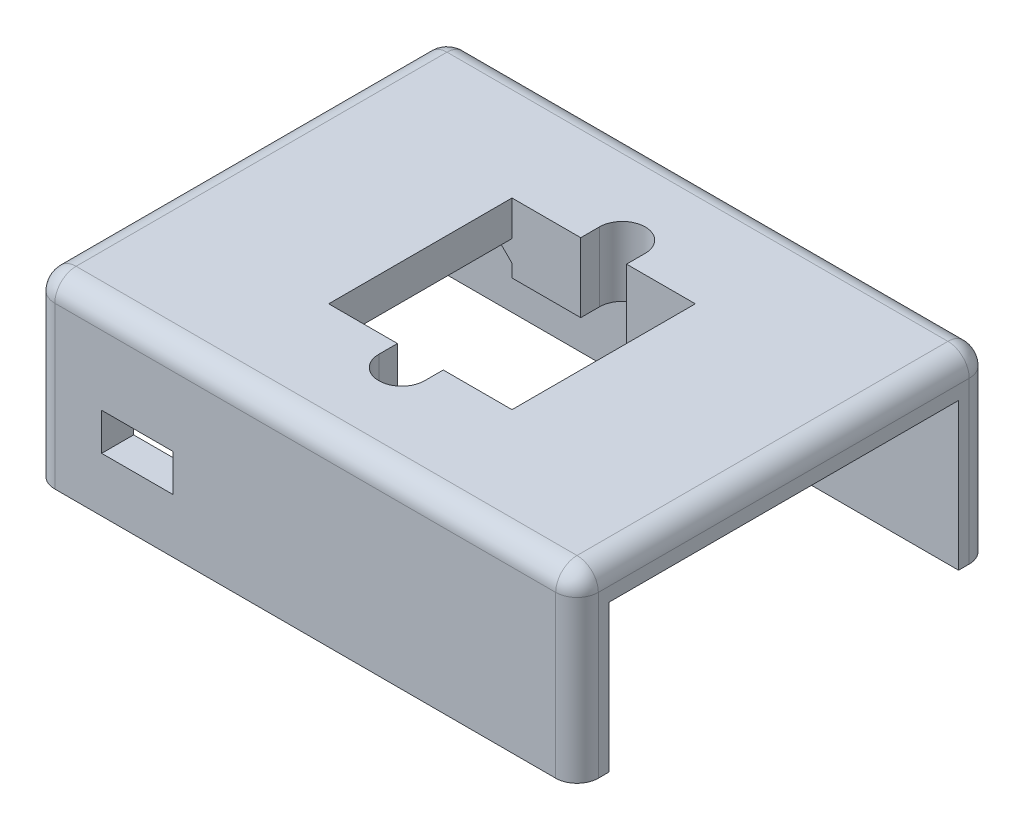
SolidWorks part; units mm, degrees
ref_plane "Alzado" through (0, 0, 0) normal (0, 0, 1) x (1, 0, 0)
ref_plane "Planta" through (0, 0, 0) normal (0, 1, 0) x (1, 0, 0)
ref_plane "Vista lateral" through (0, 0, 0) normal (1, 0, 0) x (0, 0, -1)
sketch "Croquis2" plane through (0, 0, 0) normal (0, 1, 0) x (1, 0, 0)
  line L1 (-30.5451, 30.6697) -> (20.4549, 30.6697)
  line L2 (-30.5451, 30.6697) -> (-30.5451, -8.1303)
  line L3 (-30.5451, -8.1303) -> (20.4549, -8.1303)
  line L4 (20.4549, 30.6697) -> (20.4549, -8.1303)
  dimension "D1" = 38.8
  dimension "D2" = 51
extrude "Saliente-Extruir2" add sketch "Croquis2" along normal blind 12.5
sketch "Croquis8" plane through (0, 0, 0) normal (0, -1, 0) x (1, 0, 0)
  line L0 (-30.5451, -30.6697) -> (-30.5451, 8.1303) construction
  line L1 (-27.5451, 5.1303) -> (17.4549, 5.1303)
  line L2 (-27.5451, 5.1303) -> (-27.5451, -27.6697)
  line L3 (-27.5451, -27.6697) -> (17.4549, -27.6697)
  line L4 (17.4549, 5.1303) -> (17.4549, -27.6697)
  line L5 (20.4549, 8.1303) -> (20.4549, -30.6697) construction
  line L6 (-30.5451, 8.1303) -> (20.4549, 8.1303) construction
  line L7 (20.4549, -30.6697) -> (-30.5451, -30.6697) construction
  dimension "D1" = 3
  dimension "D2" = 3
  dimension "D3" = 3
  dimension "D4" = 3
extrude "Cortar-Extruir3" cut sketch "Croquis8" against normal blind 6
sketch "Croquis10" plane through (0, 12.5, 0) normal (0, 1, 0) x (1, 0, 0)
  line L0 (-30.5451, 30.6697) -> (-30.5451, -8.1303) construction
  line L1 (-27.5451, 27.6697) -> (17.4549, 27.6697)
  line L2 (-27.5451, 27.6697) -> (-27.5451, -5.1303)
  line L3 (-27.5451, -5.1303) -> (17.4549, -5.1303)
  line L4 (17.4549, 27.6697) -> (17.4549, -5.1303)
  line L5 (20.4549, -8.1303) -> (20.4549, 30.6697) construction
  line L6 (20.4549, 30.6697) -> (-30.5451, 30.6697) construction
  line L7 (-30.5451, -8.1303) -> (20.4549, -8.1303) construction
  line L8 (-5.0451, 27.6697) -> (-5.0451, -5.1303) construction
  line L9 (-27.5451, 11.2697) -> (17.4549, 11.2697) construction
  line L11 (-13.6451, 19.8697) -> (3.5549, 19.8697)
  line L12 (-13.6451, 19.8697) -> (-13.6451, 2.6697)
  line L13 (-13.6451, 2.6697) -> (3.5549, 2.6697)
  line L14 (3.5549, 19.8697) -> (3.5549, 2.6697)
  dimension "D1" = 3
  dimension "D2" = 3
  dimension "D3" = 3
  dimension "D4" = 3
  dimension "D5" = 8.6
  dimension "D6" = 8.6
  dimension "D7" = 8.6
  dimension "D8" = 8.6
sketch "Croquis11" plane through (0, 12.5, 0) normal (0, 1, 0) x (1, 0, 0)
extrude "Cortar-Extruir4" cut sketch "Croquis10" against normal blind 10 contours L12 L11 L14 L13
sketch "Croquis12" plane through (0, 6, 0) normal (0, -1, 0) x (1, 0, 0)
  line L0 (-27.5451, -27.6697) -> (17.4549, -27.6697) construction
  line L1 (17.4549, 5.1303) -> (10.2549, 5.1303)
  line L2 (17.4549, 5.1303) -> (17.4549, -27.6697)
  line L3 (17.4549, -27.6697) -> (10.2549, -27.6697)
  line L4 (10.2549, 5.1303) -> (10.2549, -27.6697)
  dimension "D1" = 7.2
extrude "Cortar-Extruir5" cut sketch "Croquis12" against normal blind 3.2
sketch "Croquis13" plane through (0, 6, 0) normal (0, -1, 0) x (1, 0, 0)
  line L0 (-27.5451, -27.6697) -> (10.2549, -27.6697) construction
  line L1 (-27.5451, 5.1303) -> (-13.6451, 5.1303)
  line L2 (-27.5451, 5.1303) -> (-27.5451, -27.6697)
  line L3 (-27.5451, -27.6697) -> (-13.6451, -27.6697)
  line L4 (-13.6451, 5.1303) -> (-13.6451, -27.6697)
extrude "Cortar-Extruir6" cut sketch "Croquis13" against normal blind 3.2
sketch "Croquis14" plane through (20.4549, 0, 0) normal (1, 0, 0) x (0, 0, -1)
  line L0 (-8.1303, 0) -> (30.6697, 0) construction
  line L1 (-5.1303, 9.2) -> (27.6697, 9.2)
  line L2 (-5.1303, 9.2) -> (-5.1303, 0)
  line L3 (-5.1303, 0) -> (27.6697, 0)
  line L4 (27.6697, 9.2) -> (27.6697, 0)
  line L5 (-8.1303, 12.5) -> (30.6697, 12.5) construction
  line L6 (-8.1303, 12.5) -> (-8.1303, 0) construction
  line L7 (30.6697, 12.5) -> (30.6697, 0) construction
  dimension "D1" = 3.3
  dimension "D2" = 3
  dimension "D3" = 3
extrude "Cortar-Extruir7" cut sketch "Croquis14" against normal blind 3.2
sketch "Croquis16" plane through (-30.5451, 0, 0) normal (-1, 0, 0) x (0, 0, 1)
  line L0 (-30.6697, 0) -> (8.1303, 0) construction
  line L1 (-27.6697, 9.2) -> (5.1303, 9.2)
  line L2 (-27.6697, 9.2) -> (-27.6697, 0)
  line L3 (-27.6697, 0) -> (5.1303, 0)
  line L4 (5.1303, 9.2) -> (5.1303, 0)
  line L5 (-30.6697, 12.5) -> (-30.6697, 0) construction
  line L6 (8.1303, 12.5) -> (8.1303, 0) construction
  line L7 (-30.6697, 12.5) -> (8.1303, 12.5) construction
  dimension "D1" = 3
  dimension "D2" = 3
  dimension "D3" = 3.3
extrude "Cortar-Extruir8" cut sketch "Croquis16" against normal blind 3.2
sketch "Croquis17" plane through (0, 0, 0) normal (0, -1, 0) x (1, 0, 0)
  line L1 (-30.5451, 8.1303) -> (20.4549, 8.1303)
  line L2 (-30.5451, 8.1303) -> (-30.5451, 5.1303)
  line L3 (-30.5451, 5.1303) -> (20.4549, 5.1303)
  line L4 (20.4549, 8.1303) -> (20.4549, 5.1303)
  line L5 (-30.5451, -27.6697) -> (20.4549, -27.6697)
  line L6 (-30.5451, -27.6697) -> (-30.5451, -30.6697)
  line L7 (-30.5451, -30.6697) -> (20.4549, -30.6697)
  line L8 (20.4549, -27.6697) -> (20.4549, -30.6697)
extrude "Saliente-Extruir3" add sketch "Croquis17" along normal blind 4.6
sketch "Croquis18" plane through (0, 0, 8.1303) normal (0, 0, 1) x (1, 0, 0)
  line L0 (-30.5451, 12.5) -> (-30.5451, -4.6) construction
  line L1 (-24.1451, 4) -> (-17.4451, 4)
  line L2 (-24.1451, 4) -> (-24.1451, 0.5)
  line L3 (-24.1451, 0.5) -> (-17.4451, 0.5)
  line L4 (-17.4451, 4) -> (-17.4451, 0.5)
  line L5 (20.4549, -4.6) -> (-30.5451, -4.6) construction
  dimension "D1" = 6.7
  dimension "D2" = 3.5
  dimension "D3" = 6.4
  dimension "D4" = 5.1
extrude "Cortar-Extruir9" cut sketch "Croquis18" against normal blind 4.6
sketch "Croquis19" plane through (0, 0, -30.6697) normal (0, 0, -1) x (-1, 0, 0)
  line L0 (30.5451, 12.5) -> (30.5451, -4.6) construction
  line L1 (17.4451, 4) -> (24.1451, 4)
  line L2 (17.4451, 4) -> (17.4451, 0.5)
  line L3 (17.4451, 0.5) -> (24.1451, 0.5)
  line L4 (24.1451, 4) -> (24.1451, 0.5)
  line L5 (30.5451, -4.6) -> (-20.4549, -4.6) construction
  dimension "D1" = 6.7
  dimension "D2" = 3.5
  dimension "D3" = 6.4
  dimension "D4" = 5.1
sketch "Croquis20" plane through (0, 0, -30.6697) normal (0, 0, -1) x (-1, 0, 0)
extrude "Cortar-Extruir10" cut sketch "Croquis19" against normal blind 4.6
fillet "Redondeo1" radius 2 4 edges at (-30.5451, 12.5, -11.2697) (-5.0451, 12.5, 8.1303) (20.4549, 12.5, -11.2697) (-5.0451, 12.5, -30.6697)
sketch "Croquis22" plane through (0, -4.6, 0) normal (0, -1, 0) x (1, 0, 0)
  line L0 (-30.5451, -11.2697) -> (20.4549, -11.2697) construction
  line L1 (-30.5451, 5.1303) -> (-30.5451, -27.6697) construction
  line L2 (20.4549, -27.6697) -> (20.4549, 5.1303) construction
  line L3 (-30.5451, 6.6303) -> (20.4549, 6.6303) construction
  line L4 (-30.5451, 8.1303) -> (-30.5451, 5.1303) construction
  line L5 (20.4549, 5.1303) -> (20.4549, 8.1303) construction
  line L6 (20.4549, 8.1303) -> (-30.5451, 8.1303) construction
  circle A0 centre (-27.5451, 6.6303) radius 1
  circle A1 centre (-5.0451, 6.6303) radius 1
  circle A2 centre (17.4549, 6.6303) radius 1
  circle A3 centre (17.4549, -29.1697) radius 1
  circle A4 centre (-5.0451, -29.1697) radius 1
  circle A5 centre (-27.5451, -29.1697) radius 1
  dimension "D1" = 2
  dimension "D3" = 2
  dimension "D4" = 2
  dimension "D2" = 3
  dimension "D5" = 3
extrude "Cortar-Extruir11" cut sketch "Croquis22" against normal blind 2
fillet "Redondeo2" radius 2 8 edges at (-29.9593, 11.9142, 7.5445) (-29.9593, 11.9142, -30.084) (19.8691, 11.9142, -30.084) (19.8691, 11.9142, 7.5445) (-30.5451, 2.95, 8.1303) (-30.5451, 2.95, -30.6697) (20.4549, 2.95, -30.6697) (20.4549, 2.95, 8.1303)
chamfer "Chaflán1" distance 2 angle 45 2 edges at (-13.6451, 9.2, 1.2303) (-13.6451, 9.2, -23.7697)
chamfer "Chaflán2" distance 2 angle 45 1 edges at (10.2549, 9.2, -11.2697)
sketch "Croquis27" plane through (0, 12.5, 0) normal (0, 1, 0) x (1, 0, 0)
  line L0 (-13.6451, 11.2697) -> (3.5549, 11.2697) construction
  line L1 (-13.6451, 19.8697) -> (-13.6451, 2.6697) construction
  line L2 (3.5549, 19.8697) -> (3.5549, 2.6697) construction
  line L3 (-5.0451, 19.8697) -> (-5.0451, 2.6697) construction
  line L4 (-13.6451, 19.8697) -> (3.5549, 19.8697) construction
  line L5 (-13.6451, 2.6697) -> (3.5549, 2.6697) construction
  line L6 (-7.1951, 2.6697) -> (-2.8951, 2.6697)
  line L7 (-7.1951, 19.8697) -> (-2.8951, 19.8697)
  line L8 (-7.1951, 19.8697) -> (-7.1951, 21.6197)
  line L10 (-2.8951, 19.8697) -> (-2.8951, 21.6197)
  line L11 (-2.8951, 2.6697) -> (-2.8951, 0.9197)
  line L12 (-7.1951, 2.6697) -> (-7.1951, 0.9197)
  arc A0 (-7.1951, 21.6197) -> (-2.8951, 21.6197) centre (-5.0451, 21.6197) cw
  arc A1 (-7.1951, 0.9197) -> (-2.8951, 0.9197) centre (-5.0451, 0.9197) ccw
  point P17 (-5.0451, 23.7697)
  dimension "D1" = 3.9
  dimension "D2" = 2.15
  dimension "D3" = 2.15
extrude "Cortar-Extruir12" cut sketch "Croquis27" against normal blind 10
